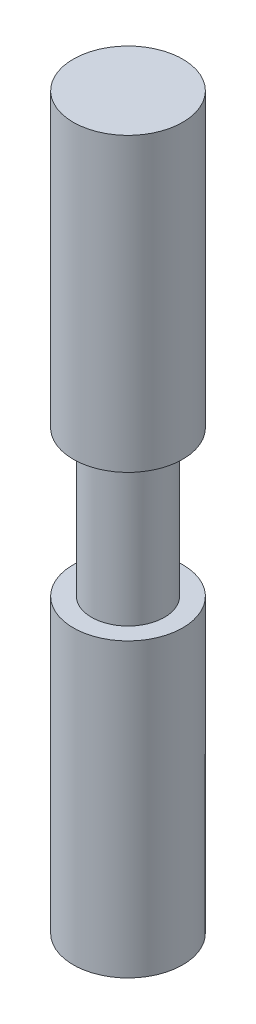
SolidWorks part; units mm, degrees
ref_plane "Front Plane" through (0, 0, 0) normal (0, 0, 1) x (1, 0, 0)
ref_plane "Top Plane" through (0, 0, 0) normal (0, 1, 0) x (1, 0, 0)
ref_plane "Right Plane" through (0, 0, 0) normal (1, 0, 0) x (0, 0, -1)
sketch "Sketch1" plane through (0, 0, 0) normal (0, 1, 0) x (1, 0, 0)
  circle A0 centre (0, 0) radius 6.35
extrude "Boss-Extrude1" add sketch "Sketch1" along normal blind 25.4
sketch "Sketch2" plane through (0, 25.4, 0) normal (0, 1, 0) x (1, 0, 0)
  circle A0 centre (0, 0) radius 9.525
extrude "Boss-Extrude2" add sketch "Sketch2" along normal blind 50.8
sketch "Sketch3" plane through (0, 0, 0) normal (0, -1, 0) x (1, 0, 0)
  circle A0 centre (0, 0) radius 9.525
extrude "Boss-Extrude3" add sketch "Sketch3" along normal blind 50.8
